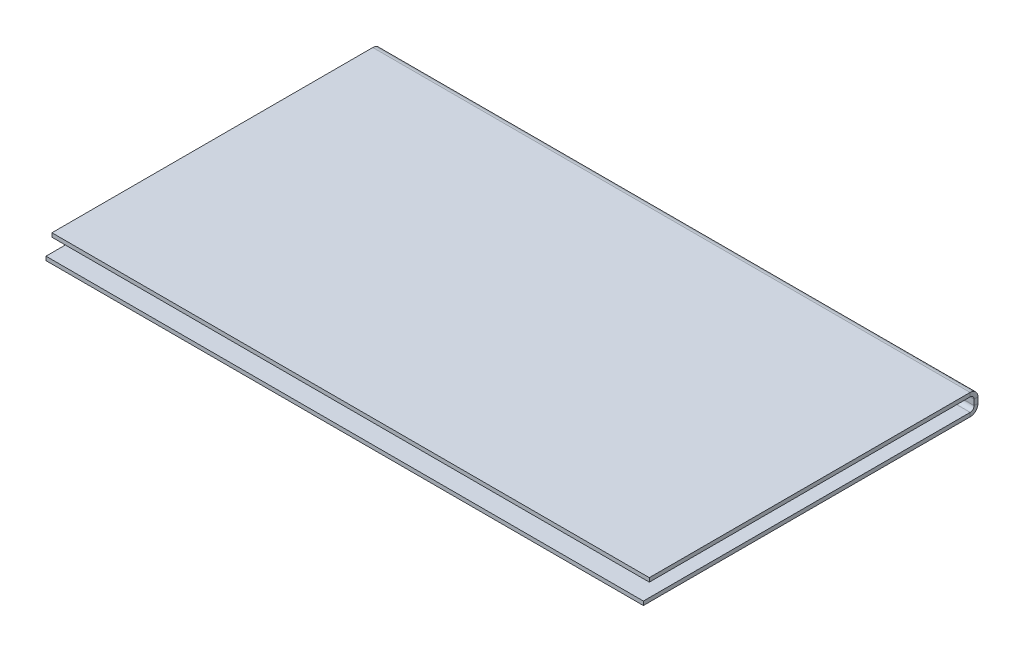
SolidWorks part; units mm, degrees
note: The reader was unsure of these and kept them because the rebuilt part matched: flange length of "Edge-Flange1", "Edge-Flange2".
ref_plane "Front Plane" through (0, 0, 0) normal (0, 0, 1) x (1, 0, 0)
ref_plane "Top Plane" through (0, 0, 0) normal (0, 1, 0) x (1, 0, 0)
ref_plane "Right Plane" through (0, 0, 0) normal (1, 0, 0) x (0, 0, -1)
sketch "Sketch1" plane through (0, 0, 0) normal (0, 1, 0) x (1, 0, 0)
  line L0 (0, 31.5604) -> (112.6868, 31.5604) construction
  line L1 (0, 0) -> (112.6868, 0)
  line L2 (0, 0) -> (0, 63.1209)
  line L3 (0, 63.1209) -> (112.6868, 63.1209)
  line L4 (112.6868, 0) -> (112.6868, 63.1209)
  circle A0 centre (50.3806, 49.9908) radius 5.4434
  circle A1 centre (50.3806, 13.13) radius 5.4434
base flange "Base-Flange1" sketch "Sketch1" thickness 0.7366 reverse thickness direction no parameters "D1"=0.7366
ref_plane "Plane1" through (112.6868, 0, -63.1209) normal (-1, 0, 0) x (0, 0, 1)
edge flange "Edge-Flange1" sketch "Sketch15" flange angle 90 flange length 4 flange position material inside bend radius 0.7366 thickness 0.7366 relief rectangular parameters "D6"=10
sketch "Sketch15" plane through (0, 0, -63.1209) normal (0, 0, 1) x (1, 0, 0)
  line L0 (112.6868, 0) -> (0, 0) construction
  line L1 (112.6868, 0) -> (0, 0)
  line L2 (112.6868, 0) -> (112.6868, 3.2634)
  line L3 (112.6868, 3.2634) -> (0, 3.2634)
  line L4 (0, 3.2634) -> (0, 0)
bend "EdgeBend1" bend radius 0.7366 bend angle 90 parameters "D5"=1
edge flange "Edge-Flange2" sketch "Sketch18" flange angle 90 flange length 62 flange position material inside bend radius 0.7366 thickness 0.7366 relief rectangular parameters "D6"=10
sketch "Sketch18" plane through (0, 3.2634, -62.3843) normal (0, -1, 0) x (1, 0, 0)
  line L2 (0, 0) -> (0, 61.2634)
  line L3 (0, 61.2634) -> (112.6868, 61.2634)
  line L4 (112.6868, 61.2634) -> (112.6868, 0)
  line L5 (112.6868, 0) -> (0, 0) construction
  line L6 (112.6868, 0) -> (0, 0)
bend "EdgeBend2" bend radius 0.7366 bend angle 90 parameters "D5"=2
sketch "Bend-Lines1" [suppressed] plane through (0, 0, 0) normal (0, 1, 0) x (1, 0, 0)
sketch "Bounding-Box1" [suppressed] plane through (0, 0, 0) normal (0, 1, 0) x (1, 0, 0)
sheet metal parameters "Sheet-Metal2" thickness 0.7366 parameters "D1"=0.7366
flat pattern "Flat-Pattern2" [suppressed]
sketch "Bend-Lines2" plane through (0, 0, 0) normal (0, 1, 0) x (1, 0, 0)
sketch3d "Bounding-Box2" [suppressed]
  line L0 (-155.4028, 65.2415, 0) -> (0, 65.2415, 0) construction
  line L1 (-155.4028, 0, 0) -> (0, 0, 0) construction
  line L2 (-155.4028, 65.2415, 0) -> (-155.4028, 0, 0) construction
  line L3 (0, 65.2415, 0) -> (0, 0, 0) construction
sheet metal parameters "Sheet-Metal3" thickness 0.7366 parameters "D1"=0.7366
flat pattern "Flat-Pattern2"
sketch "Bend-Lines2" plane through (0, 0, 0) normal (0, 1, 0) x (1, 0, 0)
  line L0 (155.4028, 64.6361) -> (0, 64.6361) construction
  line L1 (155.4028, 64.6361) -> (0, 64.6361) construction
sketch3d "Bounding-Box2" [suppressed]
  line L0 (155.4028, 76.0306, 0) -> (0, 76.0306, 0) construction
  line L1 (155.4028, 0, 0) -> (0, 0, 0) construction
  line L2 (155.4028, 76.0306, 0) -> (155.4028, 0, 0) construction
  line L3 (0, 76.0306, 0) -> (0, 0, 0) construction
bend of the flat pattern "Flatten-<EdgeBend1>1"
sheet metal parameters "Sheet-Metal4" thickness 0.7366 parameters "D1"=0.7366
flat pattern "Flat-Pattern2"
sketch "Bend-Lines2" plane through (0, 0, 0) normal (0, 1, 0) x (1, 0, 0)
  line L0 (112.6868, 62.5154) -> (0, 62.5154) construction
  line L1 (112.6868, 62.5154) -> (0, 62.5154) construction
  line L2 (112.6868, 65.3046) -> (0, 65.3046) construction
  line L3 (112.6868, 65.3046) -> (0, 65.3046) construction
sketch3d "Bounding-Box2" [suppressed]
  line L0 (0, 0, 0) -> (0, 126.6992, 0) construction
  line L1 (112.6868, 0, 0) -> (112.6868, 126.6992, 0) construction
  line L2 (0, 0, 0) -> (112.6868, 0, 0) construction
  line L3 (0, 126.6992, 0) -> (112.6868, 126.6992, 0) construction
bend of the flat pattern "Flatten-<EdgeBend1>1"
bend of the flat pattern "Flatten-<EdgeBend2>1"
